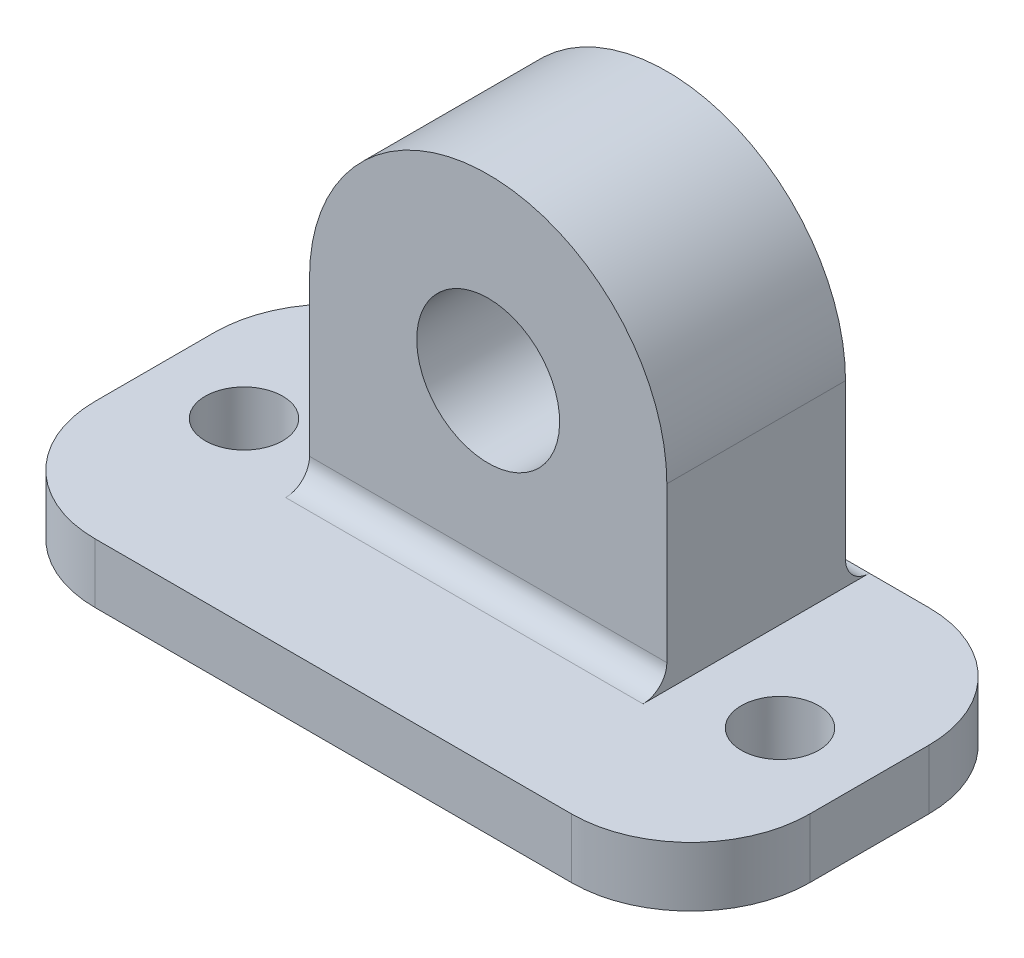
SolidWorks part; units mm, degrees
ref_plane "前视基准面" through (0, 0, 0) normal (0, 0, 1) x (1, 0, 0)
ref_plane "上视基准面" through (0, 0, 0) normal (0, 1, 0) x (1, 0, 0)
ref_plane "右视基准面" through (0, 0, 0) normal (1, 0, 0) x (0, 0, -1)
sketch "草图1" plane through (0, 0, 0) normal (0, 0, 1) x (1, 0, 0)
  line L0 (0, 25.5556) -> (0, -29.6078) construction
  line L1 (-30, 1.6667) -> (-15, 1.6667)
  line L2 (-30, 1.6667) -> (-30, -3.3333)
  line L3 (-30, -3.3333) -> (30, -3.3333)
  line L4 (30, 1.6667) -> (30, -3.3333)
  line L5 (-15, 16.6667) -> (-15, 1.6667)
  line L6 (15, 16.6667) -> (15, 1.6667)
  line L7 (15, 1.6667) -> (30, 1.6667)
  arc A0 (15, 16.6667) -> (-15, 16.6667) centre (0, 16.6667) ccw
  circle A1 centre (0, 16.6667) radius 6
  dimension "D3" = 30
  dimension "D4" = 12
  dimension "D1" = 60
  dimension "D2" = 5
extrude "凸台-拉伸1" add sketch "草图1" along normal blind 30
sketch "草图2" plane through (0, 0, 0) normal (1, 0, 0) x (0, 0, -1)
  line L0 (-30, 1.6667) -> (0, 1.6667) construction
  line L1 (-30, 31.6667) -> (-17, 31.6667)
  line L2 (-30, 31.6667) -> (-30, 1.6667)
  line L3 (-30, 1.6667) -> (-17, 1.6667)
  line L4 (-17, 31.6667) -> (-17, 1.6667)
  line L5 (-15, 35.9489) -> (-15, -10.7069) construction
  line L6 (0, 1.6667) -> (0, 16.6667) construction
  line L7 (-2, 31.6667) -> (-2, 1.6667)
  line L8 (0, 1.6667) -> (-2, 1.6667)
  line L9 (0, 31.6667) -> (0, 1.6667)
  line L10 (0, 31.6667) -> (-2, 31.6667)
  dimension "D1" = 13
  dimension "D2" = 2
extrude "切除-拉伸1" cut sketch "草图2" against normal mid plane 30
sketch "草图3" plane through (0, 0, 0) normal (0, 1, 0) x (1, 0, 0)
  line L0 (0, 6.8967) -> (0, -38.603) construction
  line L1 (-22.5, 8.7926) -> (-22.5, -36.8967) construction
  line L2 (30, 0) -> (-30, 0) construction
  line L3 (-30, -30) -> (-30, 0) construction
  line L4 (-15, -17) -> (-15, -2) construction
  line L7 (-39.3699, -15) -> (38.0428, -15) construction
  line L8 (30, -30) -> (-30, -30) construction
  circle A0 centre (-22.5, -15) radius 3.25
  circle A1 centre (22.5, -15) radius 3.25
  dimension "D1" = 6.5
extrude "切除-拉伸2" cut sketch "草图3" against normal mid plane 30
fillet "圆角1" radius 2 2 edges at (0, 1.6667, 2) (0, 1.6667, 17)
fillet "圆角2" radius 10 4 edges at (30, -0.8333, 30) (30, -0.8333, 0) (-30, -0.8333, 30) (-30, -0.8333, 0)
